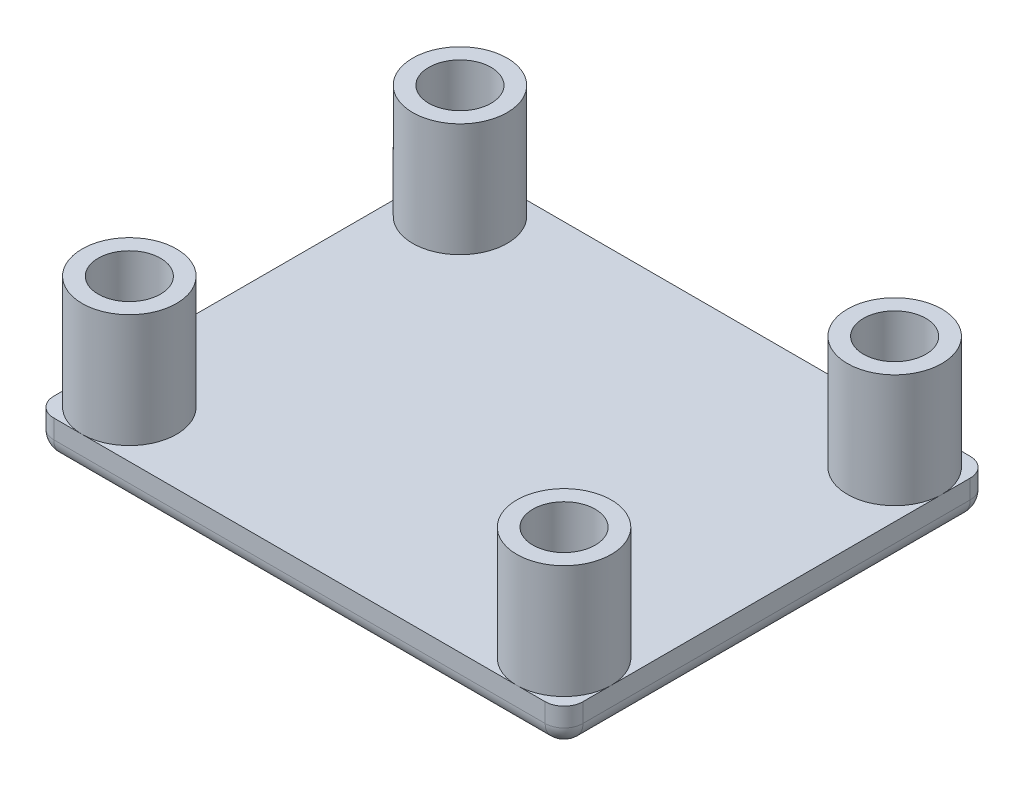
SolidWorks part; units mm, degrees
ref_plane "Alzado" through (0, 0, 0) normal (0, 0, 1) x (1, 0, 0)
ref_plane "Planta" through (0, 0, 0) normal (0, 1, 0) x (1, 0, 0)
ref_plane "Vista lateral" through (0, 0, 0) normal (1, 0, 0) x (0, 0, -1)
sketch "Croquis1" plane through (0, 0, 0) normal (0, 1, 0) x (1, 0, 0)
  line L1 (-14.005, -11.25) -> (14.005, -11.25)
  line L2 (-14.005, -11.25) -> (-14.005, 11.25)
  line L3 (-14.005, 11.25) -> (14.005, 11.25)
  line L4 (14.005, -11.25) -> (14.005, 11.25)
  line L5 (-14.005, -11.25) -> (14.005, 11.25) construction
  line L6 (-14.005, 11.25) -> (14.005, -11.25) construction
  point P0 (0, 0)
  dimension "D1" = 28.01
  dimension "D2" = 22.5
extrude "Saliente-Extruir1" add sketch "Croquis1" along normal blind 2
sketch "Croquis2" plane through (0, 2, 0) normal (0, 1, 0) x (1, 0, 0)
  line L0 (-14.005, -11.25) -> (-9.005, -11.25) construction
  line L1 (-14.005, -11.25) -> (-14.005, -6.25) construction
  line L2 (-14.005, -6.25) -> (-9.005, -6.25) construction
  line L3 (-9.005, -11.25) -> (-9.005, -6.25) construction
  line L4 (-14.005, -11.25) -> (-9.005, -6.25) construction
  line L5 (-14.005, -6.25) -> (-9.005, -11.25) construction
  line L6 (-14.005, 6.25) -> (-9.005, 6.25) construction
  line L7 (-14.005, 6.25) -> (-14.005, 11.25) construction
  line L8 (-14.005, 11.25) -> (-9.005, 11.25) construction
  line L9 (-9.005, 6.25) -> (-9.005, 11.25) construction
  line L10 (-14.005, 6.25) -> (-9.005, 11.25) construction
  line L11 (-14.005, 11.25) -> (-9.005, 6.25) construction
  line L12 (14.005, -6.25) -> (9.005, -11.25) construction
  line L13 (14.005, -11.25) -> (9.005, -6.25) construction
  line L14 (9.005, -11.25) -> (9.005, -6.25) construction
  line L15 (14.005, -6.25) -> (9.005, -6.25) construction
  line L16 (14.005, -11.25) -> (14.005, -6.25) construction
  line L17 (14.005, -11.25) -> (9.005, -11.25) construction
  line L18 (14.005, 11.25) -> (9.005, 6.25) construction
  line L19 (14.005, 6.25) -> (9.005, 11.25) construction
  line L20 (9.005, 6.25) -> (9.005, 11.25) construction
  line L21 (14.005, 11.25) -> (9.005, 11.25) construction
  line L22 (14.005, 6.25) -> (14.005, 11.25) construction
  line L23 (14.005, 6.25) -> (9.005, 6.25) construction
  line L24 (14.005, 11.25) -> (-14.005, 11.25) construction
  line L25 (14.005, -11.25) -> (14.005, 11.25) construction
  point P0 (-11.505, -8.75)
  point P5 (-11.505, 8.75)
  point P11 (11.505, -8.75)
  point P12 (11.505, 8.75)
  point P16 (11.505, -8.75)
  point P21 (11.505, 8.75)
  point P22 (-11.505, 8.75)
  point P23 (11.505, 8.75)
  point P24 (11.505, -8.75)
  point P25 (-11.505, -8.75)
  dimension "D1" = 5
  dimension "D2" = 5
  dimension "D3" = 5
  dimension "D4" = 5
  dimension "D5" = 5
  dimension "D6" = 5
  dimension "D7" = 5
  dimension "D8" = 5
  dimension "D9" = 23.01
  dimension "D10" = 23.01
  dimension "D11" = 17.5
  dimension "D12" = 17.5
sketch "Croquis3" plane through (0, 2, 0) normal (0, 1, 0) x (1, 0, 0)
  line L0 (14.005, 6.25) -> (9.005, 11.25) construction
  circle A0 centre (-11.505, 8.75) radius 2.5
  circle A1 centre (11.505, 8.75) radius 2.5
  circle A2 centre (11.505, -8.75) radius 2.5
  circle A3 centre (-11.505, -8.75) radius 2.5
  dimension "D1" = 5
  dimension "D2" = 5
  dimension "D3" = 5
  dimension "D4" = 5
extrude "Saliente-Extruir2" add sketch "Croquis3" along normal blind 6
sketch "Croquis4" plane through (0, 8, 0) normal (0, 1, 0) x (1, 0, 0)
  line L0 (-14.005, 6.25) -> (-9.005, 11.25) construction
  line L1 (14.005, 6.25) -> (9.005, 11.25) construction
  line L2 (14.005, -6.25) -> (9.005, -11.25) construction
  line L3 (-14.005, -6.25) -> (-9.005, -11.25) construction
  circle A0 centre (-11.505, 8.75) radius 1.65
  circle A1 centre (11.505, 8.75) radius 1.65
  circle A2 centre (11.505, -8.75) radius 1.65
  circle A3 centre (-11.505, -8.75) radius 1.65
  dimension "D1" = 3.3
  dimension "D2" = 3.3
  dimension "D3" = 3.3
  dimension "D4" = 3.3
extrude "Cortar-Extruir1" cut sketch "Croquis4" against normal blind 5
fillet "Redondeo1" radius 1 4 edges at (14.005, 0, 0) (0, 0, -11.25) (-14.005, 0, 0) (0, 0, 11.25)
fillet "Redondeo2" radius 1 8 edges at (13.7121, 0.2929, -10.9571) (13.7121, 0.2929, 10.9571) (-13.7121, 0.2929, 10.9571) (-13.7121, 0.2929, -10.9571) (14.005, 1.5, -11.25) (14.005, 1.5, 11.25) (-14.005, 1.5, 11.25) (-14.005, 1.5, -11.25)
